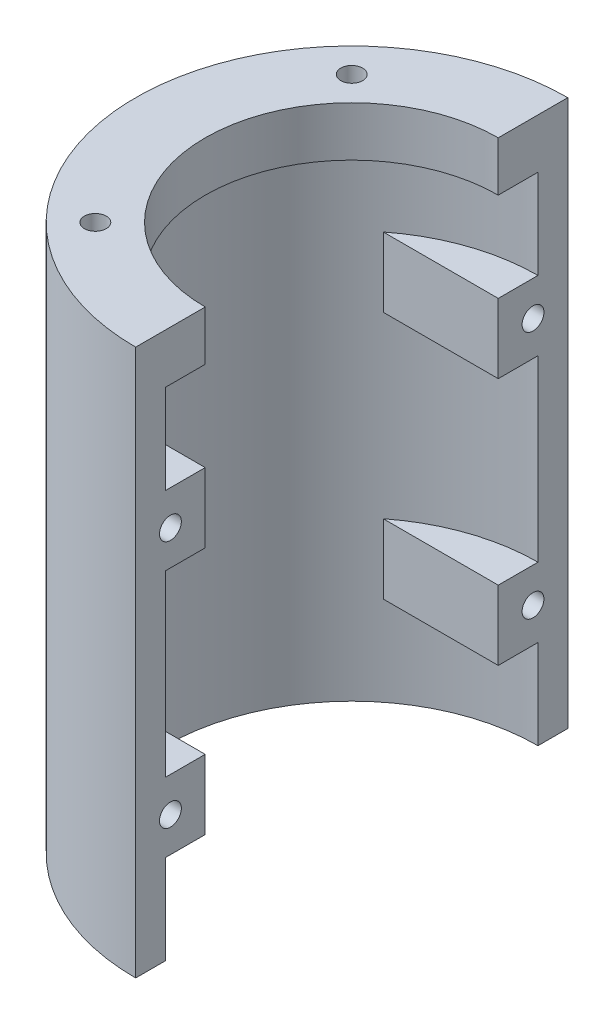
SolidWorks part; units mm, degrees
ref_plane "正面" through (0, 0, 0) normal (0, 0, 1) x (1, 0, 0)
ref_plane "平面" through (0, 0, 0) normal (0, 1, 0) x (1, 0, 0)
ref_plane "右側面" through (0, 0, 0) normal (1, 0, 0) x (0, 0, -1)
sketch "ｽｹｯﾁ1" plane through (0, 0, 0) normal (0, 1, 0) x (1, 0, 0)
  line L0 (0, -21.75) -> (0, -14.75)
  line L1 (0, -14.75) -> (0, 14.75) construction
  line L2 (0, 14.75) -> (0, 21.75)
  arc A0 (0, 21.75) -> (0, -21.75) centre (0, 0) ccw
  arc A1 (0, 14.75) -> (0, -14.75) centre (0, 0) ccw
  dimension "D1" = 14.75
  dimension "D2" = 7
extrude "ﾎﾞｽ - 押し出し1" add sketch "ｽｹｯﾁ1" along normal blind 55
sketch "ｽｹｯﾁ2" plane through (0, 55, 0) normal (0, 1, 0) x (1, 0, 0)
  circle A0 centre (0, 0) radius 14.75
  circle A1 centre (0, 0) radius 18.75
  arc A2 (0, 14.75) -> (0, -14.75) centre (0, 0) ccw construction
  arc A3 (0, 21.75) -> (0, -21.75) centre (0, 0) ccw construction
  dimension "D1" = 3
extrude "ｶｯﾄ - 押し出し1" cut sketch "ｽｹｯﾁ2" against normal through all from offset 5 offset against normal yes
sketch "ｽｹｯﾁ4" plane through (0, 0, 0) normal (1, 0, 0) x (0, 0, -1)
  line L0 (-14.75, 12.5) -> (-21.75, 12.5) construction
  line L1 (-21.75, 41) -> (-21.75, 34)
  line L2 (-18.75, 50) -> (-14.75, 50) construction
  line L3 (21.75, 55) -> (21.75, 0) construction
  line L4 (18.75, 50) -> (18.75, 0) construction
  line L5 (-21.75, 16) -> (-14.75, 16)
  line L6 (-14.75, 16) -> (-14.75, 9)
  line L7 (-14.75, 9) -> (-21.75, 9)
  line L8 (-21.75, 9) -> (-21.75, 16)
  line L9 (-21.75, 50) -> (21.75, 50) construction
  line L10 (0, 25) -> (-21.75, 25) construction
  line L11 (0, 25) -> (21.75, 25) construction
  line L12 (-21.75, 37.5) -> (21.75, 37.5) construction
  line L13 (-21.75, 0) -> (21.75, 0) construction
  line L14 (0, 50) -> (0, 0) construction
  line L15 (-18.25, 50) -> (-18.25, 0) construction
  line L16 (18.75, 50) -> (18.75, 37.5) construction
  line L17 (18.75, 37.5) -> (18.75, 25) construction
  line L18 (-21.75, 55) -> (-21.75, 0) construction
  line L19 (-21.75, 34) -> (-14.75, 34)
  line L20 (-14.75, 34) -> (-14.75, 41)
  line L21 (-14.75, 41) -> (-21.75, 41)
  line L22 (21.75, 9) -> (21.75, 16)
  line L23 (21.75, 16) -> (14.75, 16)
  line L24 (14.75, 16) -> (14.75, 9)
  line L25 (14.75, 9) -> (21.75, 9)
  line L26 (21.75, 34) -> (14.75, 34)
  line L27 (21.75, 41) -> (21.75, 34)
  line L28 (14.75, 41) -> (21.75, 41)
  line L29 (14.75, 34) -> (14.75, 41)
  circle A0 centre (-18.25, 37.5) radius 1.1 construction
  circle A1 centre (18.25, 37.5) radius 1.1 construction
  circle A2 centre (18.25, 12.5) radius 1.1 construction
  circle A3 centre (-18.25, 12.5) radius 1.1 construction
  dimension "D1" = 2.2
  dimension "D2" = 3.5
  dimension "D3" = 7
  dimension "D4" = 7
extrude "ﾎﾞｽ - 押し出し3" add sketch "ｽｹｯﾁ4" against normal up to next
sketch "ｽｹｯﾁ3" plane through (0, 0, 0) normal (1, 0, 0) x (0, 0, -1)
  line L0 (-21.75, 50) -> (21.75, 50) construction
  line L1 (0, 25) -> (-21.75, 25) construction
  line L2 (0, 25) -> (21.75, 25) construction
  line L3 (-21.75, 55) -> (-21.75, 0) construction
  line L4 (-21.75, 37.5) -> (21.75, 37.5) construction
  line L5 (21.75, 55) -> (21.75, 0) construction
  line L6 (-21.75, 0) -> (21.75, 0) construction
  line L7 (0, 50) -> (0, 0) construction
  line L8 (14.75, 50) -> (18.75, 50) construction
  line L9 (-18.25, 50) -> (-18.25, 0) construction
  line L10 (18.75, 50) -> (18.75, 37.5) construction
  line L11 (18.75, 37.5) -> (18.75, 25) construction
  line L12 (18.75, 50) -> (18.75, 41) construction
  circle A0 centre (-18.25, 37.5) radius 1.1
  circle A1 centre (18.25, 37.5) radius 1.1
  circle A2 centre (18.25, 12.5) radius 1.1
  circle A3 centre (-18.25, 12.5) radius 1.1
  dimension "D1" = 2.2
  dimension "D2" = 3.5
extrude "ｶｯﾄ - 押し出し2" cut sketch "ｽｹｯﾁ3" against normal blind 5
sketch "ｽｹｯﾁ5" plane through (0, 55, 0) normal (0, 1, 0) x (1, 0, 0)
  line L0 (0, 0) -> (-14.75, 0) construction
  line L1 (-14.75, 0) -> (-18.25, 0) construction
  line L2 (-18.25, 0) -> (-21.75, 0) construction
  line L3 (0, 0) -> (-12.9047, 12.9047) construction
  line L4 (-12.9047, -12.9047) -> (0, 0) construction
  circle A0 centre (0, 0) radius 18.25 construction
  arc A1 (0, 14.75) -> (0, -14.75) centre (0, 0) ccw construction
  arc A2 (0, 21.75) -> (0, -21.75) centre (0, 0) ccw construction
  circle A3 centre (-12.9047, -12.9047) radius 1.1
  circle A4 centre (-12.9047, 12.9047) radius 1.1
  dimension "D1" = 2.2
  dimension "D2" = 45
  dimension "D3" = 90
extrude "ｶｯﾄ - 押し出し3" cut sketch "ｽｹｯﾁ5" against normal blind 4
